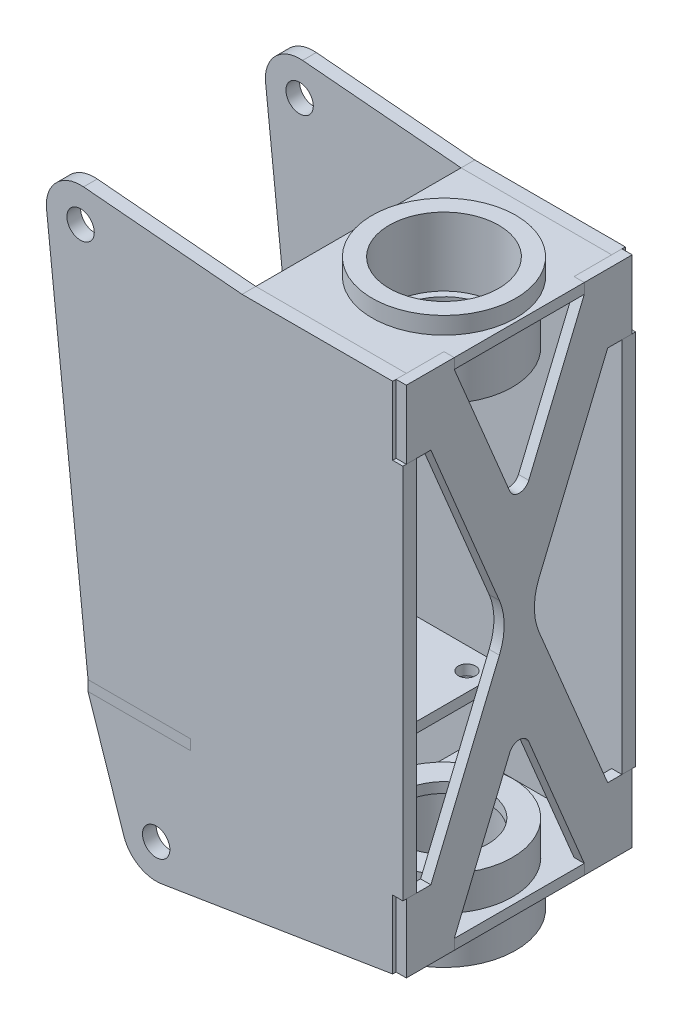
SolidWorks part; units mm, degrees
note: The reader was unsure of these and kept them because the rebuilt part matched: shared geometry of "Sketch14<3>".
other "DetailItem1"
other "DetailItem2"
other "Weld Folder"
material "AISI 1020"
ref_plane "Front Plane" through (0, 0, 0) normal (0, 0, 1) x (1, 0, 0)
ref_plane "Top Plane" through (0, 0, 0) normal (0, 1, 0) x (1, 0, 0)
ref_plane "Right Plane" through (0, 0, 0) normal (1, 0, 0) x (0, 0, -1)
sketch "Sketch5" plane through (0, 0, 0) normal (0, 1, 0) x (1, 0, 0)
  line L0 (-25, -30) -> (19, -30)
  line L1 (0, 0) -> (22, 0) construction
  line L3 (-25, 30) -> (19, 30)
  line L4 (-25, 30) -> (-25, -30)
  line L5 (19, 30) -> (19, 19)
  line L9 (22, -19) -> (22, 19)
  line L10 (19, 19) -> (22, 19)
  line L13 (19, -19) -> (22, -19)
  line L14 (19, -30) -> (19, -19)
  circle A0 centre (0, 0) radius 20
  circle A1 centre (0, 0) radius 12.5
  dimension "D3" = 40
  dimension "D14" = 25
  dimension "D9" = 22
  dimension "D11" = 3
  dimension "D12" = 25
  dimension "D13" = 11
  dimension "D16" = 60
extrude "Boss-Extrude1" add sketch "Sketch5" against normal blind 3
sketch "Sketch14" plane through (0, 0, 30) normal (0, 0, 1) x (1, 0, 0)
  line L0 (19, 0) -> (-25, 0)
  line L1 (-82.1248, -6.9941) -> (-70, -120)
  line L2 (-70, -120) -> (-40, -120)
  line L3 (-40, -120) -> (-40, -123)
  line L4 (-40, -123) -> (-70, -123)
  line L5 (-70, -123) -> (-59.5809, -154.2336)
  line L6 (-48.4948, -160.9403) -> (19, -150)
  line L7 (19, -150) -> (19, -130)
  line L8 (19, -130) -> (22, -130)
  line L9 (22, -130) -> (22, -20)
  line L10 (22, -20) -> (19, -20)
  line L11 (19, -20) -> (19, 0)
  line L12 (-25, 0) -> (-71.314, 4.035)
  arc A0 (-71.314, 4.035) -> (-82.1248, -6.9941) centre (-72.1819, -5.9273) ccw
  arc A1 (-59.5809, -154.2336) -> (-48.4948, -160.9403) centre (-50.0948, -151.0692) ccw
  circle A2 centre (-50.0948, -151.0692) radius 4
  circle A3 centre (-72.1819, -5.9273) radius 4
  circle A4 centre (-72.1819, -5.9273) radius 9.525 construction
  circle A5 centre (-50.0948, -151.0692) radius 9.525 construction
  point P9 (-62.781, -0.6094)
  point P11 (-55.7838, -142.8675)
  point P12 (-52.7881, -152.9506)
  dimension "D8" = 10
  dimension "D9" = 8
  dimension "D10" = 19.05
  dimension "D1" = 3
  dimension "D2" = 20
  dimension "D3" = 20
  dimension "D4" = 120
  dimension "D5" = 3
  dimension "D6" = 30
  dimension "D12" = 70
  dimension "D13" = 150
extrude "Boss-Extrude7" add sketch "Sketch14" along normal blind 4 separate body
extrude "Boss-Extrude11" add sketch "Sketch14<3>" along a picked direction on the side against the normal blind 4 from vertex at -60 separate body
sketch "Sketch14<3>" plane through (0, 0, 30) normal (0, 0, 1) x (1, 0, 0) same geometry as "Sketch14"
ref_plane "Plane1" through (0, -120, 0) normal (0, 1, 0) x (1, 0, 0)
sketch "Sketch15" plane through (0, -120, 0) normal (0, 1, 0) x (1, 0, 0)
  line L0 (-40.43, 0) -> (0, 0) construction
  line L1 (-11.43, 30) -> (-11.43, -30)
  line L3 (-64, -23.57) -> (-16.86, -23.57) construction
  line L4 (-64, -23.57) -> (-64, 23.57) construction
  line L5 (-64, 23.57) -> (-16.86, 23.57) construction
  line L6 (-16.86, -23.57) -> (-16.86, 23.57) construction
  line L7 (-64, -23.57) -> (-16.86, 23.57) construction
  line L8 (-64, 23.57) -> (-16.86, -23.57) construction
  line L9 (-70, -34) -> (-70, -30) construction
  line L19 (-11.43, 30) -> (-40, 30)
  line L20 (-40, 30) -> (-40, 34)
  line L21 (-40, 34) -> (-70, 34)
  line L22 (-70, 34) -> (-70, -34)
  line L23 (-70, -34) -> (-40, -34)
  line L24 (-40, -34) -> (-40, -30)
  line L25 (-40, -30) -> (-11.43, -30)
  circle A7 centre (-16.86, -23.57) radius 2.5
  circle A8 centre (-40.43, 0) radius 20
  circle A9 centre (-64, -23.57) radius 2.5
  circle A10 centre (-16.86, 23.57) radius 2.5
  circle A11 centre (-64, 23.57) radius 2.5
  point P10 (-11.43, 0)
  dimension "D1" = 40
  dimension "D5" = 5
  dimension "D2" = 47.14
  dimension "D4" = 29.57
  dimension "D6" = 60
  dimension "D7" = 4
  dimension "D8" = 28.57
  dimension "D9" = 30
extrude "Boss-Extrude12" add sketch "Sketch15" against normal blind 3 separate body
ref_plane "Plane2" through (0, -150, 0) normal (0, 1, 0) x (1, 0, 0)
sketch "Sketch7" plane through (0, -150, 0) normal (0, 1, 0) x (-1, 0, 0)
  line L1 (25, -30) -> (25, 30)
  line L15 (-19, -30) -> (25, -30)
  line L16 (25, -30) -> (25, 30)
  line L17 (25, 30) -> (-19, 30)
  line L18 (-19, 30) -> (-19, 19)
  line L19 (-19, 19) -> (-22, 19)
  line L20 (-22, 19) -> (-22, -19)
  line L21 (-22, -19) -> (-19, -19)
  line L22 (-19, -19) -> (-19, -30)
  line L23 (-19, -30) -> (25, -30)
  line L26 (25, 30) -> (-19, 30)
  line L30 (-19, 30) -> (-19, 19)
  line L31 (-19, 19) -> (-22, 19)
  line L32 (-22, 19) -> (-22, -19)
  line L34 (-22, -19) -> (-19, -19)
  line L35 (-19, -19) -> (-19, -30)
  circle A2 centre (0, 0) radius 20
  point P9 (-35, 28.5)
  point P12 (-35, -28.5)
  dimension "D3" = 40
  dimension "D4" = 0
extrude "Boss-Extrude3" add sketch "Sketch7" along normal blind 3 separate body
sketch "Sketch1" plane through (0, 0, 0) normal (1, 0, 0) x (0, 0, -1)
  line L0 (0, 0) -> (0, 72.3565) construction
  line L1 (-20, -150) -> (-20, -137)
  line L2 (-20, -150) -> (20, -150) construction
  line L3 (-21, -150) -> (-21, -160)
  line L4 (-21, 5) -> (-21, 0)
  line L6 (-21, -150) -> (-20, -150)
  line L8 (-21, 0) -> (-20, 0)
  line L9 (-20, 0) -> (-20, -18)
  line L10 (-20, -18) -> (-14, -18)
  line L11 (-14, -18) -> (-14, -15)
  line L12 (-14, -15) -> (-16, -15)
  line L13 (-16, -15) -> (-16, 5)
  line L14 (-20, -137) -> (-13, -137)
  line L15 (-13, -137) -> (-13, -140)
  line L16 (-13, -140) -> (-16, -140)
  line L17 (-16, -140) -> (-16, -160)
  line L18 (-16, -160) -> (-21, -160)
  line L19 (-16, 5) -> (-21, 5)
  dimension "D2" = 1
  dimension "D3" = 5
  dimension "D4" = 20
  dimension "D5" = 3
  dimension "D6" = 2
  dimension "D7" = 3
  dimension "D8" = 20
  dimension "D9" = 32
  dimension "D10" = 32
  dimension "D11" = 10
  dimension "D12" = 3
  dimension "D13" = 1
revolve "Revolve1" add sketch "Sketch1" angle 360 about L0
sketch "Sketch12" plane through (22, 0, 0) normal (1, 0, 0) x (0, 0, -1)
  line L0 (0, 0) -> (0, -75) construction
  line L1 (-52.1459, -75) -> (56.6369, -75) construction
  line L2 (0, -75) -> (0, -150) construction
  line L3 (21, -150) -> (-21, -150) construction
  line L4 (-33, -20) -> (-33, 0)
  line L5 (-19, -3) -> (19, -3) construction
  line L6 (-33, 0) -> (-19, 0)
  line L7 (-19, 0) -> (19, 0) construction
  line L8 (-19, 0) -> (-19, -3)
  line L9 (-19, -3) -> (-2.7692, -41.9538)
  line L10 (-33, -20) -> (-25.8333, -20)
  line L12 (-25.8333, -20) -> (-5.8013, -68.0769)
  line L13 (-19, -3) -> (19, -3) construction
  line L14 (-30, -3) -> (0, -75) construction
  line L15 (33, -20) -> (33, 0)
  line L16 (33, 0) -> (19, 0)
  line L17 (19, -3) -> (2.7692, -41.9538)
  line L18 (19, 0) -> (19, -3)
  line L19 (33, -20) -> (25.8333, -20)
  line L20 (25.8333, -20) -> (5.8013, -68.0769)
  line L21 (25.8333, -130) -> (5.8013, -81.9231)
  line L22 (33, -130) -> (25.8333, -130)
  line L23 (19, -150) -> (19, -147)
  line L24 (19, -147) -> (2.7692, -108.0462)
  line L25 (33, -150) -> (19, -150)
  line L26 (33, -130) -> (33, -150)
  line L27 (-25.8333, -130) -> (-5.8013, -81.9231)
  line L28 (-33, -130) -> (-25.8333, -130)
  line L29 (-19, -147) -> (-2.7692, -108.0462)
  line L30 (-19, -150) -> (-19, -147)
  line L31 (-33, -150) -> (-19, -150)
  line L32 (-33, -130) -> (-33, -150)
  arc A0 (2.7692, -108.0462) -> (-2.7692, -108.0462) centre (0, -109.2) ccw
  arc A1 (5.8013, -81.9231) -> (5.8013, -68.0769) centre (22.4167, -75) cw
  arc A2 (-5.8013, -68.0769) -> (-5.8013, -81.9231) centre (-22.4167, -75) cw
  arc A3 (-2.7692, -41.9538) -> (2.7692, -41.9538) centre (0, -40.8) ccw
  point P45 (0, -101.4)
  point P48 (2.9167, -75)
  point P51 (-2.9167, -75)
  point P54 (0, -48.6)
  point P62 (2.9167, -75)
  point P65 (-2.9167, -75)
  dimension "D3" = 3
  dimension "D4" = 3
  dimension "D5" = 18
  dimension "D1" = 14
  dimension "D2" = 20
extrude "Boss-Extrude6" add sketch "Sketch12" against normal blind 3 separate body
